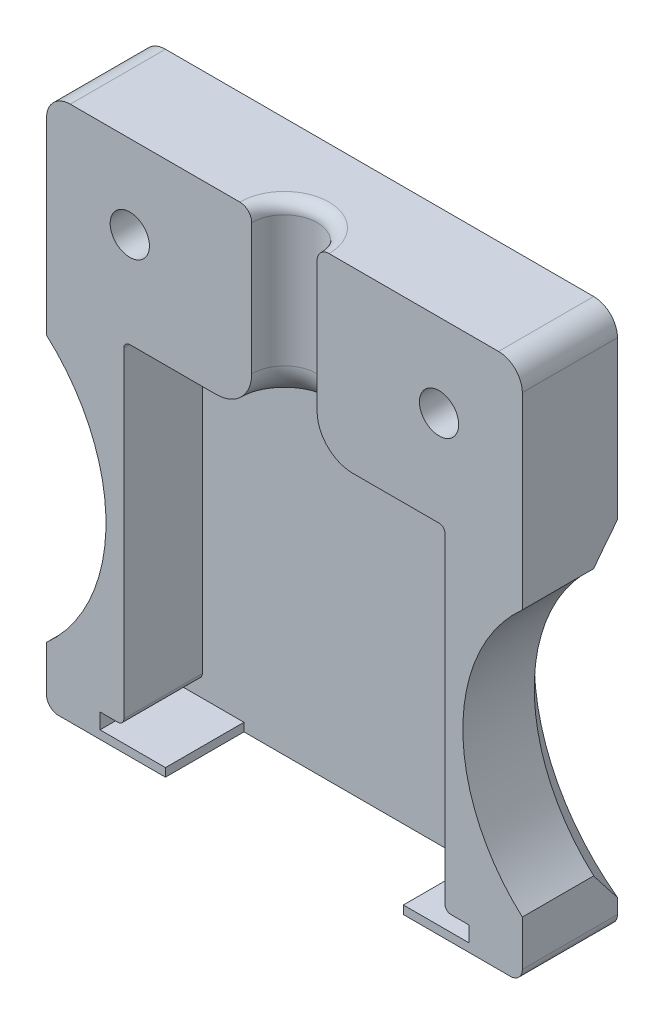
SolidWorks part; units mm, degrees
ref_plane "Alzado" through (0, 0, 0) normal (0, 0, 1) x (1, 0, 0)
ref_plane "Planta" through (0, 0, 0) normal (0, 1, 0) x (1, 0, 0)
ref_plane "Vista lateral" through (0, 0, 0) normal (1, 0, 0) x (0, 0, -1)
sketch "Croquis1" plane through (0, 0, 0) normal (0, 0, 1) x (1, 0, 0)
  line L1 (20, -22.5) -> (-20, -22.5)
  line L2 (20, -22.5) -> (20, 22.5)
  line L3 (20, 22.5) -> (-20, 22.5)
  line L4 (-20, -22.5) -> (-20, 22.5)
  line L5 (20, -22.5) -> (-20, 22.5) construction
  line L6 (20, 22.5) -> (-20, -22.5) construction
  point P0 (0, 0)
  dimension "D1" = 40
  dimension "D2" = 45
extrude "Saliente-Extruir1" add sketch "Croquis1" along normal blind 8
sketch "Croquis2" plane through (0, 0, 8) normal (0, 0, 1) x (1, 0, 0)
  line L0 (-20, -22.5) -> (20, -22.5) construction
  line L1 (15.5, -21.8) -> (-15.5, -21.8)
  line L2 (15.5, -21.8) -> (15.5, -20.5)
  line L3 (15.5, -20.5) -> (-15.5, -20.5)
  line L4 (-15.5, -21.8) -> (-15.5, -20.5)
  line L5 (15.5, -21.8) -> (-15.5, -20.5) construction
  line L6 (15.5, -20.5) -> (-15.5, -21.8) construction
  point P0 (0, -21.15)
  point P9 (0, -22.5)
  dimension "D1" = 1.3
  dimension "D2" = 0.7
  dimension "D3" = 31
extrude "Cortar-Extruir1" cut sketch "Croquis2" against normal blind 6.6
sketch "Croquis3" plane through (0, 0, 8) normal (0, 0, 1) x (1, 0, 0)
  line L0 (-20, 22.5) -> (-20, -22.5) construction
  circle A0 centre (-30, -6.5) radius 15
  circle A1 centre (30, -6.5) radius 15
  dimension "D1" = 30
  dimension "D6" = 30
  dimension "D2" = 10
  dimension "D3" = 16
  dimension "D4" = 16
  dimension "D5" = 10
extrude "Cortar-Extruir2" cut sketch "Croquis3" against normal blind 10
chamfer "Chaflán1" distance 2 angle 45 2 edges at (15, -6.5, 0) (-15, -6.5, 0)
sketch "Croquis4" plane through (0, 0, 8) normal (0, 0, 1) x (1, 0, 0)
  line L0 (-13.5, -20.5) -> (-13.5, 7.5)
  line L1 (15.5, -20.5) -> (-15.5, -20.5) construction
  line L2 (-13.5, 7.5) -> (13.5, 7.5)
  line L3 (13.5, 7.5) -> (13.5, -20.5)
  line L4 (13.5, -20.5) -> (-13.5, -20.5)
  dimension "D1" = 2
  dimension "D2" = 2
  dimension "D3" = 28
extrude "Cortar-Extruir3" cut sketch "Croquis4" against normal blind 6.6
sketch "Croquis6" plane through (0, 22.5, 0) normal (0, 1, 0) x (1, 0, 0)
  line L0 (20, -8) -> (-20, -8) construction
  circle A0 centre (0, -8) radius 2.75
  point P4 (0, 0)
  point P5 (0, -8)
  dimension "D1" = 5.5
extrude "Cortar-Extruir4" cut sketch "Croquis6" against normal blind 16.6
sketch "Croquis7" plane through (0, 0, 8) normal (0, 0, 1) x (1, 0, 0)
  circle A1 centre (13, 15.5) radius 1.65
  circle A2 centre (-13, 15.5) radius 1.65
  dimension "D1" = 3.3
  dimension "D2" = 3.3
  dimension "D3" = 7
  dimension "D4" = 7
  dimension "D5" = 7
  dimension "D6" = 7
extrude "Cortar-Extruir5" cut sketch "Croquis7" against normal blind 16.6
sketch "Croquis8" plane through (0, 0, 0) normal (0, 0, -1) x (-1, 0, 0)
  circle A0 centre (13, 15.5) radius 4
  circle A2 centre (-13, 15.5) radius 4
  dimension "D1" = 8
  dimension "D3" = 8
extrude "Cortar-Extruir6" cut sketch "Croquis8" against normal blind 4
sketch "Croquis9" plane through (0, -22.5, 0) normal (0, -1, 0) x (-1, 0, 0)
  line L0 (10, -8) -> (10, -1.4)
  line L1 (20, -8) -> (-20, -8) construction
  line L2 (10, -1.4) -> (-10, -1.4)
  line L3 (-10, -1.4) -> (-10, -8)
  line L4 (-10, -8) -> (10, -8)
  dimension "D1" = 20
  dimension "D2" = 10
  dimension "D3" = 10
  dimension "D4" = 6.6
extrude "Cortar-Extruir7" cut sketch "Croquis9" against normal blind 4
fillet "Redondeo1" radius 1 1 edges at (0, 22.5, 5.25)
fillet "Redondeo2" radius 2 2 edges at (20, 22.5, 4) (-20, 22.5, 4)
fillet "Redondeo3" radius 1 2 edges at (20, -22.5, 4) (-20, -22.5, 4)
fillet "Redondeo4" radius 3 1 edges at (0, 7.5, 5.25)
fillet "Redondeo5" radius 0.5 2 edges at (-13.5, -20.5, 4.7) (13.5, -20.5, 4.7)
fillet "Redondeo6" radius 0.5 2 edges at (13.5, 7.5, 4.7) (-13.5, 7.5, 4.7)
